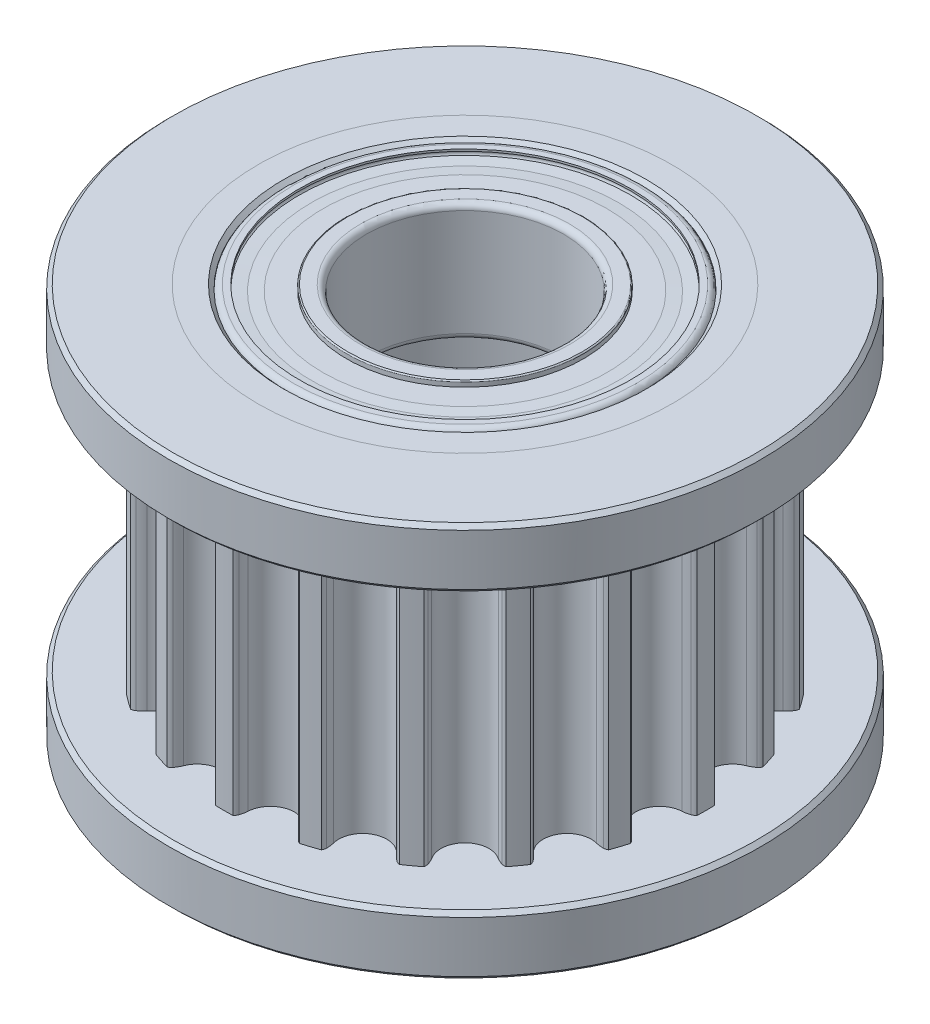
SolidWorks part; units mm, degrees
material "6061-T6 (SS)"
ref_plane "Přední rovina" through (0, 0, 0) normal (0, 0, 1) x (1, 0, 0)
ref_plane "Horní rovina" through (0, 0, 0) normal (0, 1, 0) x (1, 0, 0)
ref_plane "Pravá rovina" through (0, 0, 0) normal (1, 0, 0) x (0, 0, -1)
sketch "Skica1" plane through (0, 0, 0) normal (0, 0, 1) x (1, 0, 0)
  line L0 (4.5, 10) -> (5.25, 10)
  line L1 (5.25, 10) -> (5.25, 8.5)
  line L2 (5.25, 8.5) -> (6.11, 8.5)
  line L3 (6.11, 8.5) -> (6.11, 1.5)
  line L4 (6.11, 1.5) -> (5.25, 1.5)
  line L5 (5.25, 1.5) -> (5.25, 0)
  line L6 (5.25, 0) -> (4.5, 0)
  line L8 (4.5, 10) -> (4.5, 7)
  line L9 (4.5, 7) -> (3.5, 7)
  line L10 (3.5, 7) -> (3.5, 3)
  line L11 (3.5, 3) -> (4.5, 3)
  line L12 (4.5, 3) -> (4.5, 0)
  line L13 (0, 0) -> (0, -4.1646) construction
  dimension "D1" = 10
  dimension "D2" = 7
  dimension "D3" = 4.5
  dimension "D4" = 3.5
  dimension "D5" = 6.11
  dimension "D6" = 3
  dimension "D7" = 5.25
revolve "Rotovat1" add sketch "Skica1" angle 360 about L13
chamfer "Zkosení1" distance 0.1 angle 45 4 edges at (0, 3, 3.5) (0, 0, 4.5) (0, 7, 3.5) (0, 10, 4.5)
fillet "Zaoblit1" radius 0.1 2 edges at (0, 3, 4.5) (0, 7, 4.5)
sketch "Skica11" plane through (0, 8.5, 0) normal (0, 1, 0) x (1, 0, 0)
  line L0 (0, -5.5) -> (0, 5.5) construction
  line L1 (-5.5, 0) -> (5.5, 0) construction
  point P5 (0, 6.1087)
  arc B0 (-3.6824, -4.5256) -> (-4.5256, -3.6824) centre (-4.1938, -4.1938) ccw
  arc B1 (-3.6824, -4.5256) -> (-3.7624, -4.7003) centre (-3.1284, -4.885) ccw
  arc B2 (-3.7624, -4.7003) -> (-3.7672, -4.8088) centre (-3.5429, -4.7643) ccw
  arc B3 (-3.7672, -4.8088) -> (-3.4093, -5.0688) centre (0, 0) ccw
  arc B4 (-3.4093, -5.0688) -> (-3.3076, -5.0308) centre (-3.4362, -4.8418) ccw
  arc B5 (-3.3076, -5.0308) -> (-3.1662, -4.9006) centre (-3.6792, -4.4848) ccw
  arc B6 (-2.1037, -5.442) -> (-3.1662, -4.9006) centre (-2.6926, -5.2845) ccw
  arc B7 (-2.1037, -5.442) -> (-2.1258, -5.6329) centre (-1.4657, -5.6126) ccw
  arc B8 (-2.1258, -5.6329) -> (-2.0968, -5.7376) centre (-1.8973, -5.6259) ccw
  arc B9 (-2.0968, -5.7376) -> (-1.6761, -5.8742) centre (0, 0) ccw
  arc B10 (-1.6761, -5.8742) -> (-1.5911, -5.8066) centre (-1.7719, -5.6667) ccw
  arc B11 (-1.5911, -5.8066) -> (-1.4968, -5.6392) centre (-2.1132, -5.4022) ccw
  arc B12 (-0.319, -5.8257) -> (-1.4968, -5.6392) centre (-0.9278, -5.8579) ccw
  arc B13 (-0.319, -5.8257) -> (-0.2811, -6.0141) centre (0.3404, -5.7909) ccw
  arc B14 (-0.2811, -6.0141) -> (-0.2211, -6.1047) centre (-0.0659, -5.9369) ccw
  arc B15 (-0.2211, -6.1047) -> (0.2211, -6.1047) centre (0, 0) ccw
  arc B16 (0.2211, -6.1047) -> (0.2811, -6.0141) centre (0.0659, -5.9369) ccw
  arc B17 (0.2811, -6.0141) -> (0.319, -5.8257) centre (-0.3404, -5.7909) ccw
  arc B18 (1.4968, -5.6392) -> (0.319, -5.8257) centre (0.9278, -5.8579) ccw
  arc B19 (1.4968, -5.6392) -> (1.5911, -5.8066) centre (2.1132, -5.4022) ccw
  arc B20 (1.5911, -5.8066) -> (1.6761, -5.8742) centre (1.7719, -5.6667) ccw
  arc B21 (1.6761, -5.8742) -> (2.0968, -5.7376) centre (0, 0) ccw
  arc B22 (2.0968, -5.7376) -> (2.1258, -5.6329) centre (1.8973, -5.6259) ccw
  arc B23 (2.1258, -5.6329) -> (2.1037, -5.442) centre (1.4657, -5.6126) ccw
  arc B24 (3.1662, -4.9006) -> (2.1037, -5.442) centre (2.6926, -5.2845) ccw
  arc B25 (3.1662, -4.9006) -> (3.3076, -5.0308) centre (3.6792, -4.4848) ccw
  arc B26 (3.3076, -5.0308) -> (3.4093, -5.0688) centre (3.4362, -4.8418) ccw
  arc B27 (3.4093, -5.0688) -> (3.7672, -4.8088) centre (0, 0) ccw
  arc B28 (3.7672, -4.8088) -> (3.7624, -4.7003) centre (3.5429, -4.7643) ccw
  arc B29 (3.7624, -4.7003) -> (3.6824, -4.5256) centre (3.1284, -4.885) ccw
  arc B30 (4.5256, -3.6824) -> (3.6824, -4.5256) centre (4.1938, -4.1938) ccw
  arc B31 (4.5256, -3.6824) -> (4.7003, -3.7624) centre (4.885, -3.1284) ccw
  arc B32 (4.7003, -3.7624) -> (4.8088, -3.7672) centre (4.7643, -3.5429) ccw
  arc B33 (4.8088, -3.7672) -> (5.0688, -3.4093) centre (0, 0) ccw
  arc B34 (5.0688, -3.4093) -> (5.0308, -3.3076) centre (4.8418, -3.4362) ccw
  arc B35 (5.0308, -3.3076) -> (4.9006, -3.1662) centre (4.4848, -3.6792) ccw
  arc B36 (5.442, -2.1037) -> (4.9006, -3.1662) centre (5.2845, -2.6926) ccw
  arc B37 (5.442, -2.1037) -> (5.6329, -2.1258) centre (5.6126, -1.4657) ccw
  arc B38 (5.6329, -2.1258) -> (5.7376, -2.0968) centre (5.6259, -1.8973) ccw
  arc B39 (5.7376, -2.0968) -> (5.8742, -1.6761) centre (0, 0) ccw
  arc B40 (5.8742, -1.6761) -> (5.8066, -1.5911) centre (5.6667, -1.7719) ccw
  arc B41 (5.8066, -1.5911) -> (5.6392, -1.4968) centre (5.4022, -2.1132) ccw
  arc B42 (5.8257, -0.319) -> (5.6392, -1.4968) centre (5.8579, -0.9278) ccw
  arc B43 (5.8257, -0.319) -> (6.0141, -0.2811) centre (5.7909, 0.3404) ccw
  arc B44 (6.0141, -0.2811) -> (6.1047, -0.2211) centre (5.9369, -0.0659) ccw
  arc B45 (6.1047, -0.2211) -> (6.1047, 0.2211) centre (0, 0) ccw
  arc B46 (6.1047, 0.2211) -> (6.0141, 0.2811) centre (5.9369, 0.0659) ccw
  arc B47 (6.0141, 0.2811) -> (5.8257, 0.319) centre (5.7909, -0.3404) ccw
  arc B48 (5.6392, 1.4968) -> (5.8257, 0.319) centre (5.8579, 0.9278) ccw
  arc B49 (5.6392, 1.4968) -> (5.8066, 1.5911) centre (5.4022, 2.1132) ccw
  arc B50 (5.8066, 1.5911) -> (5.8742, 1.6761) centre (5.6667, 1.7719) ccw
  arc B51 (5.8742, 1.6761) -> (5.7376, 2.0968) centre (0, 0) ccw
  arc B52 (5.7376, 2.0968) -> (5.6329, 2.1258) centre (5.6259, 1.8973) ccw
  arc B53 (5.6329, 2.1258) -> (5.442, 2.1037) centre (5.6126, 1.4657) ccw
  arc B54 (4.9006, 3.1662) -> (5.442, 2.1037) centre (5.2845, 2.6926) ccw
  arc B55 (4.9006, 3.1662) -> (5.0308, 3.3076) centre (4.4848, 3.6792) ccw
  arc B56 (5.0308, 3.3076) -> (5.0688, 3.4093) centre (4.8418, 3.4362) ccw
  arc B57 (5.0688, 3.4093) -> (4.8088, 3.7672) centre (0, 0) ccw
  arc B58 (4.8088, 3.7672) -> (4.7003, 3.7624) centre (4.7643, 3.5429) ccw
  arc B59 (4.7003, 3.7624) -> (4.5256, 3.6824) centre (4.885, 3.1284) ccw
  arc B60 (3.6824, 4.5256) -> (4.5256, 3.6824) centre (4.1938, 4.1938) ccw
  arc B61 (3.6824, 4.5256) -> (3.7624, 4.7003) centre (3.1284, 4.885) ccw
  arc B62 (3.7624, 4.7003) -> (3.7672, 4.8088) centre (3.5429, 4.7643) ccw
  arc B63 (3.7672, 4.8088) -> (3.4093, 5.0688) centre (0, 0) ccw
  arc B64 (3.4093, 5.0688) -> (3.3076, 5.0308) centre (3.4362, 4.8418) ccw
  arc B65 (3.3076, 5.0308) -> (3.1662, 4.9006) centre (3.6792, 4.4848) ccw
  arc B66 (2.1037, 5.442) -> (3.1662, 4.9006) centre (2.6926, 5.2845) ccw
  arc B67 (2.1037, 5.442) -> (2.1258, 5.6329) centre (1.4657, 5.6126) ccw
  arc B68 (2.1258, 5.6329) -> (2.0968, 5.7376) centre (1.8973, 5.6259) ccw
  arc B69 (2.0968, 5.7376) -> (1.6761, 5.8742) centre (0, 0) ccw
  arc B70 (1.6761, 5.8742) -> (1.5911, 5.8066) centre (1.7719, 5.6667) ccw
  arc B71 (1.5911, 5.8066) -> (1.4968, 5.6392) centre (2.1132, 5.4022) ccw
  arc B72 (0.319, 5.8257) -> (1.4968, 5.6392) centre (0.9278, 5.8579) ccw
  arc B73 (0.319, 5.8257) -> (0.2811, 6.0141) centre (-0.3404, 5.7909) ccw
  arc B74 (0.2811, 6.0141) -> (0.2211, 6.1047) centre (0.0659, 5.9369) ccw
  arc B75 (0.2211, 6.1047) -> (-0.2211, 6.1047) centre (0, 0) ccw
  arc B76 (-0.2211, 6.1047) -> (-0.2811, 6.0141) centre (-0.0659, 5.9369) ccw
  arc B77 (-0.2811, 6.0141) -> (-0.319, 5.8257) centre (0.3404, 5.7909) ccw
  arc B78 (-1.4968, 5.6392) -> (-0.319, 5.8257) centre (-0.9278, 5.8579) ccw
  arc B79 (-1.4968, 5.6392) -> (-1.5911, 5.8066) centre (-2.1132, 5.4022) ccw
  arc B80 (-1.5911, 5.8066) -> (-1.6761, 5.8742) centre (-1.7719, 5.6667) ccw
  arc B81 (-1.6761, 5.8742) -> (-2.0968, 5.7376) centre (0, 0) ccw
  arc B82 (-2.0968, 5.7376) -> (-2.1258, 5.6329) centre (-1.8973, 5.6259) ccw
  arc B83 (-2.1258, 5.6329) -> (-2.1037, 5.442) centre (-1.4657, 5.6126) ccw
  arc B84 (-3.1662, 4.9006) -> (-2.1037, 5.442) centre (-2.6926, 5.2845) ccw
  arc B85 (-3.1662, 4.9006) -> (-3.3076, 5.0308) centre (-3.6792, 4.4848) ccw
  arc B86 (-3.3076, 5.0308) -> (-3.4093, 5.0688) centre (-3.4362, 4.8418) ccw
  arc B87 (-3.4093, 5.0688) -> (-3.7672, 4.8088) centre (0, 0) ccw
  arc B88 (-3.7672, 4.8088) -> (-3.7624, 4.7003) centre (-3.5429, 4.7643) ccw
  arc B89 (-3.7624, 4.7003) -> (-3.6824, 4.5256) centre (-3.1284, 4.885) ccw
  arc B90 (-4.5256, 3.6824) -> (-3.6824, 4.5256) centre (-4.1938, 4.1938) ccw
  arc B91 (-4.5256, 3.6824) -> (-4.7003, 3.7624) centre (-4.885, 3.1284) ccw
  arc B92 (-4.7003, 3.7624) -> (-4.8088, 3.7672) centre (-4.7643, 3.5429) ccw
  arc B93 (-4.8088, 3.7672) -> (-5.0688, 3.4093) centre (0, 0) ccw
  arc B94 (-5.0688, 3.4093) -> (-5.0308, 3.3076) centre (-4.8418, 3.4362) ccw
  arc B95 (-5.0308, 3.3076) -> (-4.9006, 3.1662) centre (-4.4848, 3.6792) ccw
  arc B96 (-5.442, 2.1037) -> (-4.9006, 3.1662) centre (-5.2845, 2.6926) ccw
  arc B97 (-5.442, 2.1037) -> (-5.6329, 2.1258) centre (-5.6126, 1.4657) ccw
  arc B98 (-5.6329, 2.1258) -> (-5.7376, 2.0968) centre (-5.6259, 1.8973) ccw
  arc B99 (-5.7376, 2.0968) -> (-5.8742, 1.6761) centre (0, 0) ccw
  arc B100 (-5.8742, 1.6761) -> (-5.8066, 1.5911) centre (-5.6667, 1.7719) ccw
  arc B101 (-5.8066, 1.5911) -> (-5.6392, 1.4968) centre (-5.4022, 2.1132) ccw
  arc B102 (-5.8257, 0.319) -> (-5.6392, 1.4968) centre (-5.8579, 0.9278) ccw
  arc B103 (-5.8257, 0.319) -> (-6.0141, 0.2811) centre (-5.7909, -0.3404) ccw
  arc B104 (-6.0141, 0.2811) -> (-6.1047, 0.2211) centre (-5.9369, 0.0659) ccw
  arc B105 (-6.1047, 0.2211) -> (-6.1047, -0.2211) centre (0, 0) ccw
  arc B106 (-6.1047, -0.2211) -> (-6.0141, -0.2811) centre (-5.9369, -0.0659) ccw
  arc B107 (-6.0141, -0.2811) -> (-5.8257, -0.319) centre (-5.7909, 0.3404) ccw
  arc B108 (-5.6392, -1.4968) -> (-5.8257, -0.319) centre (-5.8579, -0.9278) ccw
  arc B109 (-5.6392, -1.4968) -> (-5.8066, -1.5911) centre (-5.4022, -2.1132) ccw
  arc B110 (-5.8066, -1.5911) -> (-5.8742, -1.6761) centre (-5.6667, -1.7719) ccw
  arc B111 (-5.8742, -1.6761) -> (-5.7376, -2.0968) centre (0, 0) ccw
  arc B112 (-5.7376, -2.0968) -> (-5.6329, -2.1258) centre (-5.6259, -1.8973) ccw
  arc B113 (-5.6329, -2.1258) -> (-5.442, -2.1037) centre (-5.6126, -1.4657) ccw
  arc B114 (-4.9006, -3.1662) -> (-5.442, -2.1037) centre (-5.2845, -2.6926) ccw
  arc B115 (-4.9006, -3.1662) -> (-5.0308, -3.3076) centre (-4.4848, -3.6792) ccw
  arc B116 (-5.0308, -3.3076) -> (-5.0688, -3.4093) centre (-4.8418, -3.4362) ccw
  arc B117 (-5.0688, -3.4093) -> (-4.8088, -3.7672) centre (0, 0) ccw
  arc B118 (-4.8088, -3.7672) -> (-4.7003, -3.7624) centre (-4.7643, -3.5429) ccw
  arc B119 (-4.7003, -3.7624) -> (-4.5256, -3.6824) centre (-4.885, -3.1284) ccw
sketch_block_instance "Blok1-1"
sketch_block "Blok1"
extrude "Odebrat vysunutím1" cut sketch "Skica11" against normal through all flip side to cut
sketch "Skica10" plane through (0, 10, 0) normal (0, 1, 0) x (1, 0, 0)
  circle A0 centre (0, 0) radius 7.5
  circle A1 centre (0, 0) radius 5.25 construction
  circle A2 centre (0, 0) radius 5.25
  dimension "D1" = 15
extrude "Přidat vysunutím1" add sketch "Skica10" against normal up to surface (1.5 mm away) separate body up to face at (0, 8.5, 5.25)
sketch "Skica12" plane through (0, 0, 0) normal (0, -1, 0) x (1, 0, 0)
  circle A0 centre (0, 0) radius 7.5
  circle A1 centre (0, 0) radius 5.25 construction
  circle A2 centre (0, 0) radius 5.25
  circle A3 centre (0, 0) radius 7.5 construction
extrude "Přidat vysunutím2" add sketch "Skica12" against normal up to surface (1.5 mm away) separate body up to face at (0, 1.5, 5.25)
chamfer "Zkosení2" distance 0.1 angle 45 2 edges at (0, 8.5, -7.5) (0, 10, 7.5)
chamfer "Zkosení3" distance 0.1 angle 45 2 edges at (0, 0, -7.5) (0, 1.5, 7.5)
sketch "Skica4" plane through (0, 0, 0) normal (0, 0, 1) x (1, 0, 0)
  line L0 (4.5, 9.85) -> (4.5, 7.15)
  line L1 (4.35, 7) -> (4.2, 7)
  line L2 (4.2, 7) -> (4.2, 7.05)
  line L3 (3.85, 7.2828) -> (4.2132, 7.229)
  line L4 (3.85, 7.2828) -> (3.85, 8.0528)
  line L5 (3.85, 8.9472) -> (3.85, 9.7172)
  line L6 (3.85, 9.7172) -> (4.2132, 9.771)
  line L7 (4.35, 10) -> (4.2, 10)
  line L8 (4.2, 10) -> (4.2, 9.95)
  line L9 (0, 0) -> (0, 18.4294) construction
  line L10 (4.4, 7) -> (-4.4, 7) construction
  arc A0 (4.35, 10) -> (4.5, 9.85) centre (4.35, 9.85) cw
  arc A1 (4.35, 7) -> (4.5, 7.15) centre (4.35, 7.15) ccw
  arc A2 (4.2, 9.95) -> (4.2132, 9.771) centre (4.2, 9.86) cw
  arc A3 (3.85, 8.9472) -> (3.85, 8.0528) centre (3.45, 8.5) cw
  arc A4 (4.2, 7.05) -> (4.2132, 7.229) centre (4.2, 7.14) ccw
  point P26 (4.5, 8.5)
  point P29 (4.275, 7)
  dimension "D3" = 0.09
  dimension "D6" = 0.15
  dimension "D7" = 0.6
  dimension "D1" = 4.5
  dimension "D2" = 3.85
  dimension "D4" = 0.05
  dimension "D5" = 0.15
  dimension "D8" = 0.77
  dimension "D9" = 3
  dimension "D10" = 1.05
revolve "Rotovat2" add sketch "Skica4" angle 360 about L9
sketch "Skica5" plane through (0, 0, 0) normal (0, 0, 1) x (1, 0, 0)
  line L0 (2.5, 9.85) -> (2.5, 7.15)
  line L1 (2.65, 10) -> (2.97, 10)
  line L2 (3, 9.97) -> (3, 9.86)
  line L3 (3, 9.86) -> (3.6, 9.86)
  line L4 (3.6, 9.86) -> (3.9, 9.84)
  line L5 (3.9, 9.84) -> (4.2, 9.86)
  line L6 (4.2, 9.86) -> (4.2, 9.81)
  line L7 (4.2, 9.81) -> (3.9, 9.77)
  line L8 (3.9, 9.77) -> (3.6, 9.77)
  line L9 (3.6, 9.77) -> (3, 9.81)
  line L10 (3, 9.81) -> (3, 8.8969)
  line L11 (2.65, 7) -> (2.97, 7)
  line L12 (0, 0) -> (0, 20.363) construction
  line L13 (3, 7.03) -> (3, 7.14)
  line L21 (3, 7.19) -> (3, 8.1031)
  line L22 (3, 7.14) -> (3.6, 7.14)
  line L23 (3.6, 7.14) -> (3.8962, 7.1917)
  line L24 (3.8962, 7.1917) -> (4.1924, 7.14)
  line L25 (4.1924, 7.14) -> (4.1924, 7.19)
  line L26 (4.1924, 7.19) -> (3.8975, 7.2581)
  line L27 (3.8975, 7.2581) -> (3.5975, 7.2581)
  line L28 (3.5975, 7.2581) -> (3, 7.19)
  line L29 (-4.2, 7) -> (4.2, 7) construction
  arc A0 (2.65, 7) -> (2.5, 7.15) centre (2.65, 7.15) cw
  arc A1 (2.65, 10) -> (2.5, 9.85) centre (2.65, 9.85) ccw
  arc A2 (3, 9.97) -> (2.97, 10) centre (2.97, 9.97) ccw
  arc A3 (3, 7.03) -> (2.97, 7) centre (2.97, 7.03) cw
  arc A4 (3, 8.8969) -> (3, 8.1031) centre (3.45, 8.5) ccw
  dimension "D3" = 0.15
  dimension "D4" = 0.11
  dimension "D5" = 0.03
  dimension "D7" = 0.6
  dimension "D1" = 2.5
  dimension "D2" = 3
  dimension "D6" = 0.6
  dimension "D8" = 0.95
  dimension "D9" = 3
  dimension "D10" = 1.2
  dimension "D11" = 0.3
  dimension "D12" = 0.05
  dimension "D13" = 0.9
  dimension "D14" = 0.6
  dimension "D15" = 0.09
  dimension "D16" = 0.05
  dimension "D17" = 0.05
revolve "Rotovat3" add sketch "Skica5" angle 360 about L12
sketch "Skica6" plane through (0, 0, 0) normal (0, 0, 1) x (1, 0, 0)
  line L0 (3.45, 9.1) -> (3.45, 7.9)
  line L4 (-4.2, 7) -> (4.2, 7) construction
  arc A0 (3.45, 9.1) -> (3.45, 7.9) centre (3.45, 8.5) cw
  dimension "D1" = 0.6
  dimension "D2" = 1.5
  dimension "D3" = 3.45
revolve "Rotovat4" add sketch "Skica6" angle 360 about L0
pattern_circular "Kruhové pole1" count 8 over 360 about axis through (0, 0, 0) along (0, 1, 0) of bodies 105
sketch "Skica7" plane through (0, 0, 0) normal (0, 0, 1) x (1, 0, 0)
  line L0 (4.5, 2.85) -> (4.5, 0.15)
  line L1 (4.35, 0) -> (4.2, 0)
  line L2 (4.2, 0) -> (4.2, 0.05)
  line L3 (3.85, 0.2828) -> (4.2132, 0.229)
  line L4 (3.85, 0.2828) -> (3.85, 1.0528)
  line L5 (3.85, 1.9472) -> (3.85, 2.7172)
  line L6 (3.85, 2.7172) -> (4.2132, 2.771)
  line L7 (4.35, 3) -> (4.2, 3)
  line L8 (4.2, 3) -> (4.2, 2.95)
  line L9 (0, 0) -> (0, 11.2374) construction
  arc A0 (4.35, 3) -> (4.5, 2.85) centre (4.35, 2.85) cw
  arc A1 (4.35, 0) -> (4.5, 0.15) centre (4.35, 0.15) ccw
  arc A2 (4.2, 2.95) -> (4.2132, 2.771) centre (4.2, 2.86) cw
  arc A3 (3.85, 1.9472) -> (3.85, 1.0528) centre (3.45, 1.5) cw
  arc A4 (4.2, 0.05) -> (4.2132, 0.229) centre (4.2, 0.14) ccw
  point P19 (4.5, 1.5)
  point P20 (4.275, 0)
  dimension "D1" = 0.09
  dimension "D4" = 0.15
  dimension "D5" = 0.6
  dimension "D2" = 0.05
  dimension "D3" = 0.15
  dimension "D6" = 0.77
  dimension "D7" = 3
  dimension "D8" = 1.05
  dimension "D9" = 4.5
  dimension "D10" = 3.85
revolve "Rotovat5" add sketch "Skica7" angle 360 about L9
sketch "Skica8" plane through (0, 0, 0) normal (0, 0, 1) x (1, 0, 0)
  line L0 (2.5, 2.85) -> (2.5, 0.15)
  line L1 (2.65, 3) -> (2.97, 3)
  line L2 (3, 2.97) -> (3, 2.86)
  line L3 (3, 2.86) -> (3.6, 2.86)
  line L4 (3.6, 2.86) -> (3.9, 2.84)
  line L5 (3.9, 2.84) -> (4.2, 2.86)
  line L6 (4.2, 2.86) -> (4.2, 2.81)
  line L7 (4.2, 2.81) -> (3.9, 2.77)
  line L8 (3.9, 2.77) -> (3.6, 2.77)
  line L9 (3.6, 2.77) -> (3, 2.81)
  line L10 (3, 2.81) -> (3, 1.8969)
  line L11 (2.65, 0) -> (2.97, 0)
  line L12 (3, 0.03) -> (3, 0.14)
  line L13 (3, 0.19) -> (3, 1.1031)
  line L14 (3, 0.14) -> (3.6, 0.14)
  line L15 (3.6, 0.14) -> (3.8962, 0.1917)
  line L16 (3.8962, 0.1917) -> (4.1924, 0.14)
  line L17 (4.1924, 0.14) -> (4.1924, 0.19)
  line L18 (4.1924, 0.19) -> (3.8975, 0.2581)
  line L19 (3.8975, 0.2581) -> (3.5975, 0.2581)
  line L20 (3.5975, 0.2581) -> (3, 0.19)
  line L21 (0, 0) -> (0, -2.9362) construction
  arc A0 (2.65, 0) -> (2.5, 0.15) centre (2.65, 0.15) cw
  arc A1 (2.65, 3) -> (2.5, 2.85) centre (2.65, 2.85) ccw
  arc A2 (3, 2.97) -> (2.97, 3) centre (2.97, 2.97) ccw
  arc A3 (3, 0.03) -> (2.97, 0) centre (2.97, 0.03) cw
  arc A4 (3, 1.8969) -> (3, 1.1031) centre (3.45, 1.5) ccw
  dimension "D1" = 0.15
  dimension "D2" = 0.03
  dimension "D5" = 0.6
  dimension "D3" = 0.11
  dimension "D4" = 0.6
  dimension "D6" = 0.95
  dimension "D7" = 3
  dimension "D8" = 1.2
  dimension "D9" = 0.3
  dimension "D10" = 0.05
  dimension "D11" = 0.9
  dimension "D12" = 0.6
  dimension "D13" = 0.09
  dimension "D14" = 0.05
  dimension "D15" = 0.05
  dimension "D16" = 2.5
  dimension "D17" = 3
revolve "Rotovat6" add sketch "Skica8" angle 360 about L21
sketch "Skica9" plane through (0, 0, 0) normal (0, 0, 1) x (1, 0, 0)
  line L0 (3.45, 2.1) -> (3.45, 0.9)
  line L1 (0, -2.351) -> (0, 5.6956) construction
  arc A0 (3.45, 2.1) -> (3.45, 0.9) centre (3.45, 1.5) cw
  dimension "D1" = 0.6
  dimension "D2" = 3.45
  dimension "D3" = 1.5
revolve "Rotovat7" add sketch "Skica9" angle 360 about L0
pattern_circular "Kruhové pole3" count 8 over 360 about axis through (0, 0, 0) along (0, 1, 0) reverse direction yes of bodies 123
